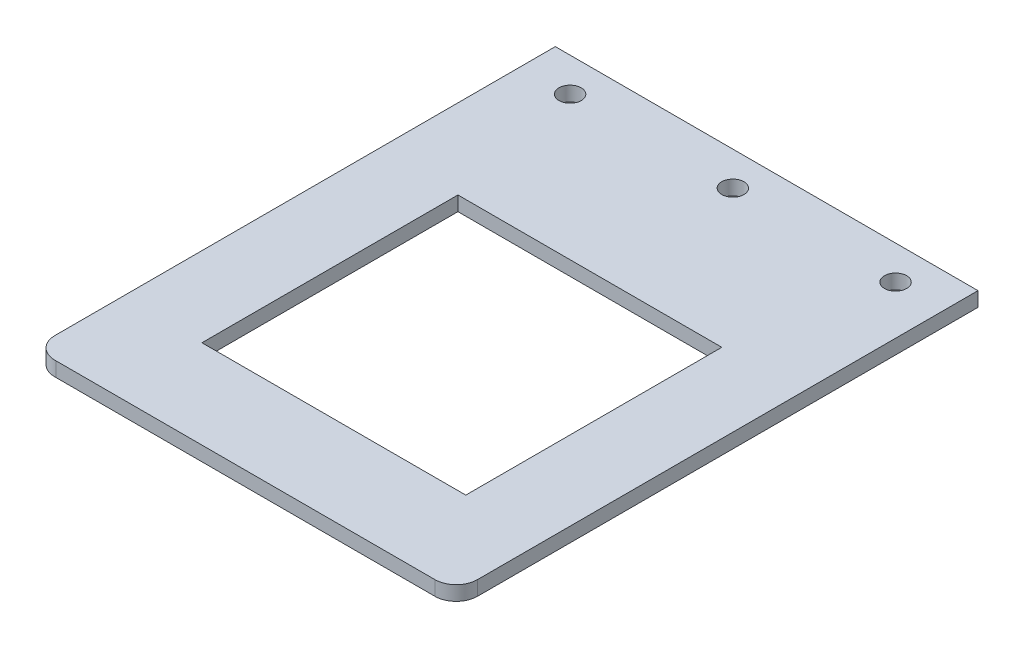
SolidWorks part; units mm, degrees
ref_plane "Front Plane" through (0, 0, 0) normal (0, 0, 1) x (1, 0, 0)
ref_plane "Top Plane" through (0, 0, 0) normal (0, 1, 0) x (1, 0, 0)
ref_plane "Right Plane" through (0, 0, 0) normal (1, 0, 0) x (0, 0, -1)
sketch "Sketch1" plane through (0, 0, 0) normal (0, 1, 0) x (1, 0, 0)
  line L9 (-22.8759, -25.5118) -> (16.3453, -25.5118)
  line L10 (-16.9379, -16.3429) -> (10.3671, -16.3429)
  line L11 (10.3671, -16.3429) -> (10.3671, 10.1491)
  line L12 (10.3671, 10.1491) -> (-16.9379, 10.1491)
  line L13 (-16.9379, 10.1491) -> (-16.9379, -16.3429)
  line L16 (-14.2871, 14.6854) -> (12.9539, 14.6854)
  line L17 (12.9539, 14.6854) -> (12.9539, 18.4324)
  line L18 (12.9539, 18.4324) -> (-14.2871, 18.4324)
  line L19 (-14.2871, 18.4324) -> (-14.2871, 14.6854)
  line L22 (-25.1937, -23.3118) -> (-25.1937, 28.4832)
  line L23 (18.5453, 28.4832) -> (18.5453, -23.3118)
  line L24 (-25.1937, 28.4832) -> (18.5453, 28.4832)
  circle A0 centre (-20.1649, 24.9832) radius 1.15
  circle A1 centre (-3.3249, 24.9832) radius 1.15
  circle A2 centre (13.5151, 24.9832) radius 1.15
  arc A3 (-25.1937, -23.3118) -> (-22.8759, -25.5118) centre (-22.9907, -23.3118) ccw
  arc A4 (18.5453, -23.3118) -> (16.3453, -25.5118) centre (16.3453, -23.3118) cw
extrude "Boss-Extrude1" add sketch "Sketch1" along normal blind 1.5
sketch "Sketch2" plane through (0, 1.5, 0) normal (0, 1, 0) x (1, 0, 0)
  line L0 (-14.2871, 18.4324) -> (12.9539, 18.4324)
  line L1 (12.9539, 18.4324) -> (12.9539, 14.6854)
  line L2 (12.9539, 14.6854) -> (-14.2871, 14.6854)
  line L3 (-14.2871, 14.6854) -> (-14.2871, 18.4324)
  line L4 (18.5453, 28.4832) -> (-25.1937, 28.4832)
  line L5 (-25.1937, 28.4832) -> (-25.1937, -23.3118)
  line L6 (-22.8759, -25.5118) -> (16.3453, -25.5118)
  line L7 (18.5453, -23.3118) -> (18.5453, 28.4832)
  line L8 (18.5453, 28.4832) -> (-25.1937, 28.4832)
  line L9 (-25.1937, 28.4832) -> (-25.1937, -23.3118)
  line L10 (-22.8759, -25.5118) -> (16.3453, -25.5118)
  line L11 (18.5453, -23.3118) -> (18.5453, 28.4832)
  arc A2 (-25.1937, -23.3118) -> (-22.8759, -25.5118) centre (-22.9907, -23.3118) ccw
  arc A3 (16.3453, -25.5118) -> (18.5453, -23.3118) centre (16.3453, -23.3118) ccw
  arc A4 (-25.1937, -23.3118) -> (-22.8759, -25.5118) centre (-22.9907, -23.3118) ccw
  arc A5 (16.3453, -25.5118) -> (18.5453, -23.3118) centre (16.3453, -23.3118) ccw
  dimension "D1" = 0
extrude "Boss-Extrude2" add sketch "Sketch2" along normal blind 2 separate body contours L3 L0 L1 L2
sketch "Sketch3" plane through (0, 1.5, 0) normal (0, -1, 0) x (1, 0, 0)
  line L4 (12.9539, -14.6854) -> (-14.2871, -14.6854)
  line L5 (-14.2871, -14.6854) -> (-14.2871, -18.4324)
  line L6 (-14.2871, -18.4324) -> (12.9539, -18.4324)
  line L7 (12.9539, -18.4324) -> (12.9539, -14.6854)
  line L8 (12.9539, -14.6854) -> (-14.2871, -14.6854)
  line L9 (-14.2871, -14.6854) -> (-14.2871, -18.4324)
  line L10 (-14.2871, -18.4324) -> (12.9539, -18.4324)
  line L11 (12.9539, -18.4324) -> (12.9539, -14.6854)
  dimension "D1" = 0
extrude "Boss-Extrude3" add sketch "Sketch3" along normal up to surface (1.5 mm away) up to face at (-3.3249, 0, -23.8332)
sketch "Sketch5" plane through (0, 0, 0) normal (0, -1, 0) x (1, 0, 0)
  line L0 (-14.2871, -18.4324) -> (-9.2871, -18.4324)
  line L1 (-9.2871, -18.4324) -> (-9.2871, -14.6854)
  line L2 (12.9539, -18.4324) -> (7.9539, -18.4324)
  line L3 (7.9539, -18.4324) -> (7.9539, -14.6854)
  line L4 (12.9539, -14.6854) -> (-14.2871, -14.6854)
  line L5 (12.9539, -18.4324) -> (12.9539, -14.6854)
  line L6 (-14.2871, -18.4324) -> (12.9539, -18.4324)
  line L7 (-14.2871, -14.6854) -> (-14.2871, -18.4324)
  line L8 (12.9539, -14.6854) -> (-14.2871, -14.6854)
  line L9 (12.9539, -18.4324) -> (12.9539, -14.6854)
  line L10 (-14.2871, -18.4324) -> (12.9539, -18.4324)
  line L11 (-14.2871, -14.6854) -> (-14.2871, -18.4324)
  line L12 (7.9539, -14.6854) -> (-9.2871, -14.6854)
  line L13 (-9.2871, -18.4324) -> (7.9539, -18.4324)
  dimension "D1" = 0
extrude "Boss-Extrude4" add sketch "Sketch5" along normal blind 2 contours L1 L10 L3 L8 region at (-0.6666, 0, -16.5589)
sketch "Sketch6" plane through (0, 3.5, 0) normal (0, 1, 0) x (1, 0, 0)
  line L4 (-14.2871, 14.6854) -> (12.9539, 14.6854)
  line L5 (12.9539, 14.6854) -> (12.9539, 18.4324)
  line L6 (12.9539, 18.4324) -> (-14.2871, 18.4324)
  line L7 (-14.2871, 18.4324) -> (-14.2871, 14.6854)
  line L8 (-14.2871, 14.6854) -> (12.9539, 14.6854)
  line L9 (12.9539, 14.6854) -> (12.9539, 18.4324)
  line L10 (12.9539, 18.4324) -> (-14.2871, 18.4324)
  line L11 (-14.2871, 18.4324) -> (-14.2871, 14.6854)
  dimension "D1" = 0
extrude "Cut-Extrude1" cut sketch "Sketch6" against normal up to surface (2 mm away) up to face at (-0.6666, 1.5, -16.5589)
